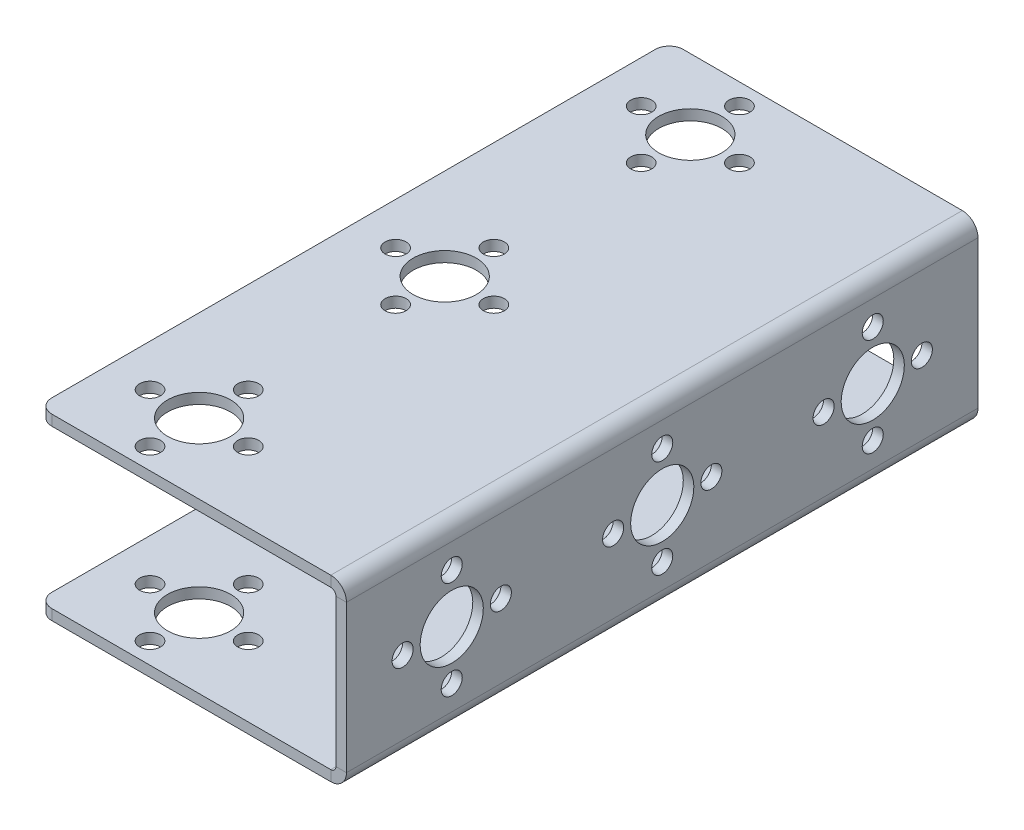
SolidWorks part; units mm, degrees
note: The reader was unsure of these and kept them because the rebuilt part matched: flange length of "Edge-Flange1", "Edge-Flange2".
ref_plane "Front Plane" through (0, 0, 0) normal (0, 0, 1) x (1, 0, 0)
ref_plane "Top Plane" through (0, 0, 0) normal (0, 1, 0) x (1, 0, 0)
ref_plane "Right Plane" through (0, 0, 0) normal (1, 0, 0) x (0, 0, -1)
sketch "Sketch1" plane through (0, 0, 0) normal (0, 1, 0) x (1, 0, 0)
  line L0 (0, 0) -> (-22, 0) construction
  line L1 (0, 45) -> (-44, 45)
  line L2 (0, 45) -> (0, -45)
  line L3 (0, -45) -> (-44, -45)
  line L4 (-44, 45) -> (-44, -45)
  line L5 (0, 45) -> (-44, -45) construction
  line L6 (0, -45) -> (-44, 45) construction
  point P4 (-22, 0)
  dimension "D1" = 90
  dimension "D2" = 44
base flange "Base-Flange1" sketch "Sketch1" thickness 1.5 reverse thickness direction yes parameters "D1"=0.7366
edge flange "Edge-Flange1" sketch "Sketch8" flange angle 90 flange length 24 flange position material inside bend radius 0.7366 thickness 1.5 relief rectangular parameters "D6"=10
sketch "Sketch8" plane through (0, 1.5, 0) normal (1, 0, 0) x (0, 0, -1)
  line L2 (-45, 0) -> (-45, 24)
  line L3 (-45, 24) -> (45, 24)
  line L4 (45, 24) -> (45, 0)
  line L7 (-45, 0) -> (45, 0) construction
  line L8 (-45, 0) -> (45, 0)
bend "EdgeBend1" bend radius 0.7366 bend angle 90 parameters "D5"=1
edge flange "Edge-Flange2" sketch "Sketch11" flange angle 90 flange length 42.5 flange position material inside bend radius 0.7366 thickness 1.5 relief rectangular parameters "D6"=10
sketch "Sketch11" plane through (-1.5, 25.5, 0) normal (0, 1, 0) x (0, 0, -1)
  line L0 (45, 0) -> (-45, 0) construction
  line L1 (45, 0) -> (-45, 0)
  line L2 (-45, 0) -> (-45, 42.5)
  line L3 (-45, 42.5) -> (45, 42.5)
  line L4 (45, 42.5) -> (45, 0)
bend "EdgeBend2" bend radius 0.7366 bend angle 90 parameters "D5"=2
sketch "Sketch12" plane through (0, 0, 0) normal (0, 1, 0) x (1, 0, 0)
  line L1 (-2.2366, 45) -> (-44, 45) construction
  line L2 (-31, 35) -> (-31, -45) construction
  line L3 (-44, -45) -> (-2.2366, -45) construction
  line L4 (-44, 45) -> (-44, -45) construction
  circle A0 centre (-31, 35) radius 4.5
  circle A1 centre (-31, 42) radius 1.5
  circle A2 centre (-31, 28) radius 1.5
  circle A3 centre (-24, 35) radius 1.5
  circle A4 centre (-38, 35) radius 1.5
  circle A5 centre (-31, 0) radius 4.5
  circle A6 centre (-31, 7) radius 1.5
  circle A7 centre (-31, -7) radius 1.5
  circle A8 centre (-24, 0) radius 1.5
  circle A9 centre (-38, 0) radius 1.5
  circle A10 centre (-31, -35) radius 4.5
  circle A11 centre (-31, -28) radius 1.5
  circle A12 centre (-24, -35) radius 1.5
  circle A13 centre (-38, -35) radius 1.5
  circle A14 centre (-31, -42) radius 1.5
  point P18 (-31, -35)
  point P38 (-31, 0.1385)
  point P39 (0, 0)
  point P41 (-31, -41.3956)
  dimension "D1" = 9
  dimension "D2" = 3
  dimension "D13" = 9
  dimension "D14" = 3
  dimension "D15" = 9
  dimension "D16" = 3
  dimension "D3" = 7
  dimension "D4" = 7
  dimension "D5" = 7
  dimension "D6" = 7
  dimension "D7" = 13
  dimension "D8" = 10
  dimension "D9" = 10
  dimension "D10" = 14
  dimension "D11" = 7
  dimension "D12" = 7
  dimension "D17" = 7
  dimension "D18" = 7
  dimension "D19" = 7
  dimension "D20" = 7
  dimension "D21" = 7
extrude "Cut-Extrude4" cut sketch "Sketch12" along normal through all normal cut yes
sketch "Sketch13" plane through (-1.5, 0, 0) normal (-1, 0, 0) x (0, 0, 1)
  line L0 (0, 0) -> (0, 25.5) construction
  line L2 (-45, 25.5) -> (45, 25.5) construction
  circle A0 centre (0, 12.75) radius 4.5
  circle A1 centre (0, 19.75) radius 1.5
  circle A2 centre (0, 5.75) radius 1.5
  circle A3 centre (7, 12.75) radius 1.5
  circle A4 centre (-7, 12.75) radius 1.5
  dimension "D1" = 9
  dimension "D2" = 3
  dimension "D3" = 7
  dimension "D4" = 7
  dimension "D5" = 7
  dimension "D6" = 7
extrude "Cut-Extrude5" cut sketch "Sketch13" against normal blind 10 normal cut yes
pattern_linear "LPattern1" count 2 spacing 30 along (0, 0, -1) count 2 spacing 30 along (0, 0, 1) of "Cut-Extrude5"
fillet "Fillet1" radius 2 4 edges at (-44, 24.75, -45) (-44, 0.75, -45) (-44, 0.75, 45) (-44, 24.75, 45)
sketch "Bend-Lines1" [suppressed] plane through (0, 0, 0) normal (0, 1, 0) x (1, 0, 0)
sketch "Bounding-Box1" [suppressed] plane through (0, 0, 0) normal (0, 1, 0) x (1, 0, 0)
sheet metal parameters "Sheet-Metal2" thickness 1.5 parameters "D1"=0.7366
flat pattern "Flat-Pattern2" [suppressed]
sketch "Bend-Lines2" plane through (0, 0, 0) normal (0, 1, 0) x (1, 0, 0)
sketch3d "Bounding-Box2" [suppressed]
  line L0 (-44, -45, 0) -> (-44, 45, 0) construction
  line L1 (0, -45, 0) -> (0, 45, 0) construction
  line L2 (-44, -45, 0) -> (0, -45, 0) construction
  line L3 (-44, 45, 0) -> (0, 45, 0) construction
sheet metal parameters "Sheet-Metal3" thickness 1.5 parameters "D1"=0.7366
flat pattern "Flat-Pattern2"
sketch "Bend-Lines2" plane through (0, 0, 0) normal (0, -1, 0) x (-1, 0, 0)
  line L0 (1.069, 45) -> (1.069, -45) construction
  line L1 (1.069, 45) -> (1.069, -45) construction
sketch3d "Bounding-Box2" [suppressed]
  line L0 (44, -45, 0) -> (44, 45, 0) construction
  line L1 (-23.3619, -45, 0) -> (-23.3619, 45, 0) construction
  line L2 (44, -45, 0) -> (-23.3619, -45, 0) construction
  line L3 (44, 45, 0) -> (-23.3619, 45, 0) construction
bend of the flat pattern "Flatten-<EdgeBend1>1"
sheet metal parameters "Sheet-Metal4" thickness 1.5 parameters "D1"=0.7366
flat pattern "Flat-Pattern2"
sketch "Bend-Lines2" plane through (0, 0, 0) normal (0, -1, 0) x (-1, 0, 0)
  line L0 (1.069, 45) -> (1.069, -45) construction
  line L1 (1.069, 45) -> (1.069, -45) construction
  line L2 (-22.2929, 45) -> (-22.2929, -45) construction
  line L3 (-22.2929, 45) -> (-22.2929, -45) construction
sketch3d "Bounding-Box2" [suppressed]
  line L0 (-65.2239, 45, 0) -> (44, 45, 0) construction
  line L1 (-65.2239, -45, 0) -> (44, -45, 0) construction
  line L2 (-65.2239, 45, 0) -> (-65.2239, -45, 0) construction
  line L3 (44, 45, 0) -> (44, -45, 0) construction
bend of the flat pattern "Flatten-<EdgeBend1>1"
bend of the flat pattern "Flatten-<EdgeBend2>1"
sheet metal parameters "Sheet-Metal5" thickness 1.5 parameters "D1"=0.7366
flat pattern "Flat-Pattern2"
sketch "Bend-Lines2" plane through (0, 0, 0) normal (0, -1, 0) x (-1, 0, 0)
  line L0 (1.069, 45) -> (1.069, -45) construction
  line L1 (1.069, 45) -> (1.069, -45) construction
  line L2 (-22.2929, 45) -> (-22.2929, -45) construction
  line L3 (-22.2929, 45) -> (-22.2929, -45) construction
sketch3d "Bounding-Box2" [suppressed]
  line L0 (-65.2239, 45, 0) -> (44, 45, 0) construction
  line L1 (-65.2239, -45, 0) -> (44, -45, 0) construction
  line L2 (-65.2239, 45, 0) -> (-65.2239, -45, 0) construction
  line L3 (44, 45, 0) -> (44, -45, 0) construction
bend of the flat pattern "Flatten-<EdgeBend1>1"
bend of the flat pattern "Flatten-<EdgeBend2>1"
sheet metal parameters "Sheet-Metal6" thickness 1.5 parameters "D1"=0.7366
flat pattern "Flat-Pattern2"
sketch "Bend-Lines2" plane through (0, 0, 0) normal (0, -1, 0) x (-1, 0, 0)
  line L0 (1.069, 45) -> (1.069, -45) construction
  line L1 (1.069, 45) -> (1.069, -45) construction
  line L2 (-22.2929, 45) -> (-22.2929, -45) construction
  line L3 (-22.2929, 45) -> (-22.2929, -45) construction
sketch3d "Bounding-Box2" [suppressed]
  line L0 (-65.2239, 45, 0) -> (44, 45, 0) construction
  line L1 (-65.2239, -45, 0) -> (44, -45, 0) construction
  line L2 (-65.2239, 45, 0) -> (-65.2239, -45, 0) construction
  line L3 (44, 45, 0) -> (44, -45, 0) construction
bend of the flat pattern "Flatten-<EdgeBend1>1"
bend of the flat pattern "Flatten-<EdgeBend2>1"
sheet metal parameters "Sheet-Metal7" thickness 1.5 parameters "D1"=0.7366
flat pattern "Flat-Pattern2"
sketch "Bend-Lines2" plane through (0, 0, 0) normal (0, -1, 0) x (-1, 0, 0)
  line L0 (1.069, 45) -> (1.069, -45) construction
  line L1 (1.069, 45) -> (1.069, -45) construction
  line L2 (-22.2929, 45) -> (-22.2929, -45) construction
  line L3 (-22.2929, 45) -> (-22.2929, -45) construction
sketch3d "Bounding-Box2" [suppressed]
  line L0 (44, 44.9999, 0) -> (-65.2239, 45, 0) construction
  line L1 (44, -45, 0) -> (-65.2239, -44.9999, 0) construction
  line L2 (44, 44.9999, 0) -> (44, -45, 0) construction
  line L3 (-65.2239, 45, 0) -> (-65.2239, -44.9999, 0) construction
bend of the flat pattern "Flatten-<EdgeBend1>1"
bend of the flat pattern "Flatten-<EdgeBend2>1"
